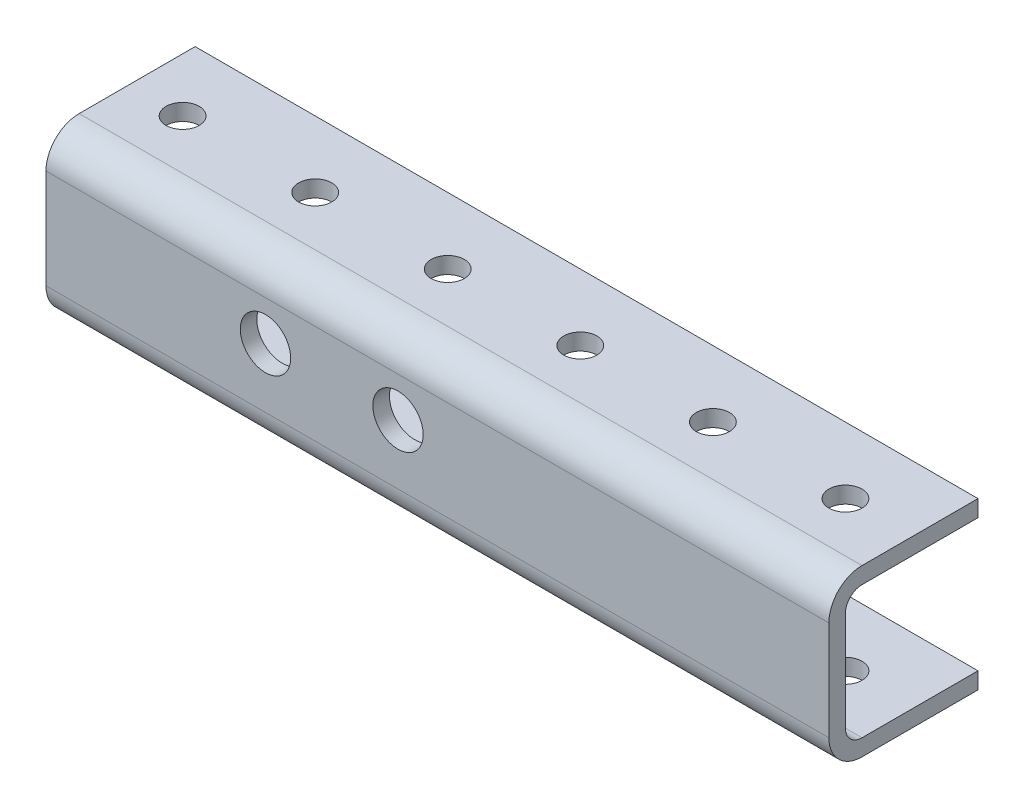
SolidWorks part; units mm, degrees
ref_plane "Front Plane" through (0, 0, 0) normal (0, 0, 1) x (1, 0, 0)
ref_plane "Top Plane" through (0, 0, 0) normal (0, 1, 0) x (1, 0, 0)
ref_plane "Right Plane" through (0, 0, 0) normal (1, 0, 0) x (0, 0, -1)
ref_plane "Plane1" through (0, 0, 3.175) normal (0, 0, 1) x (1, 0, 0)
sketch "Sketch1" plane through (0, 0, 3.175) normal (0, 0, 1) x (1, 0, 0)
  line L0 (872.98, -7.202) -> (872.98, 24.548)
  line L1 (872.98, 24.548) -> (-16.02, 24.548)
  line L2 (-16.02, 24.548) -> (-16.02, -7.202)
  line L3 (-16.02, -7.202) -> (872.98, -7.202)
extrude "Extrude1" add sketch "Sketch1" against normal blind 28.575
sketch "Sketch2" plane through (-16.02, 0, 0) normal (-1, 0, 0) x (0, 0, 1)
  line L0 (-25.4, 21.373) -> (-25.4, -4.027)
  line L1 (-25.4, -4.027) -> (0, -4.027)
  line L2 (0, -4.027) -> (0, 21.373)
  line L3 (0, 21.373) -> (-25.4, 21.373)
extrude "Extrude2" cut sketch "Sketch2" against normal up to next
hole_wizard "Hole1" positions "Sketch4" profile "Sketch3" legacy
sketch "Sketch4" plane through (0, 24.548, 0) normal (0, 1, 0) x (-1, 0, 0)
  point P0 (3.32, -12.7)
sketch "Sketch3" plane through (-3.32, 24.548, -12.7) normal (1, 0, 0) x (0, 0, 1)
  line L0 (0, 0) -> (0, 3.175)
  line L1 (0, 3.175) -> (3.175, 3.175)
  line L2 (3.175, 3.175) -> (3.175, 0)
  line L3 (3.175, 0) -> (0, 0)
  line L4 (0, 110) -> (0, -10) construction
  dimension "Diameter" = 6.35
  dimension "Depth" = 3.175
sketch3d "3DSketch1"
  point P0 (428.6664, 8.6668, -7.2024)
  point P1 (528.6664, 8.6668, -7.2024)
ref_axis "Axis1" through (528.6664, 8.6668, -7.2024) along (-1, 0, 0)
pattern_linear "LPattern1" count 35 spacing 25.4 along (1, 0, 0) of "Hole1"
hole_wizard "Hole2" positions "Sketch6" profile "Sketch5" legacy
sketch "Sketch6" plane through (0, 0, 3.175) normal (0, 0, 1) x (1, 0, 0)
  point P0 (66.53, 10.578)
sketch "Sketch5" plane through (66.53, 10.578, 3.175) normal (1, 0, 0) x (0, -1, 0)
  line L0 (0, 0) -> (0, 3.175)
  line L1 (0, 3.175) -> (4.826, 3.175)
  line L2 (4.826, 3.175) -> (4.826, 0)
  line L3 (4.826, 0) -> (0, 0)
  line L4 (0, 110) -> (0, -10) construction
  dimension "Diameter" = 9.652
  dimension "Depth" = 3.175
sketch3d "3DSketch2"
  point P0 (428.8468, 8.4517, -7.1294)
  point P1 (528.8468, 8.4517, -7.1294)
ref_axis "Axis2" through (528.8468, 8.4517, -7.1294) along (-1, 0, 0)
pattern_linear "LPattern2" count 12 spacing 25.4 along (1, 0, 0) skipping (2, 0), (3, 0), (4, 0), (5, 0), (6, 0), (7, 0), (8, 0), (9, 0) of "Hole2"
hole_wizard "Hole3" positions "Sketch8" profile "Sketch7" legacy
sketch "Sketch8" plane through (0, 0, 3.175) normal (0, 0, 1) x (1, 0, 0)
  point P0 (428.48, 6.768)
sketch "Sketch7" plane through (428.48, 6.768, 3.175) normal (1, 0, 0) x (0, -1, 0)
  line L0 (0, 0) -> (0, 3.175)
  line L1 (0, 3.175) -> (4.826, 3.175)
  line L2 (4.826, 3.175) -> (4.826, 0)
  line L3 (4.826, 0) -> (0, 0)
  line L4 (0, 110) -> (0, -10) construction
  dimension "Diameter" = 9.652
  dimension "Depth" = 3.175
hole_wizard "Hole4" positions "Sketch10" profile "Sketch9" legacy
sketch "Sketch10" plane through (0, 0, 3.175) normal (0, 0, 1) x (1, 0, 0)
  point P0 (511.03, 10.578)
sketch "Sketch9" plane through (511.03, 10.578, 3.175) normal (1, 0, 0) x (0, -1, 0)
  line L0 (0, 0) -> (0, 3.175)
  line L1 (0, 3.175) -> (4.826, 3.175)
  line L2 (4.826, 3.175) -> (4.826, 0)
  line L3 (4.826, 0) -> (0, 0)
  line L4 (0, 110) -> (0, -10) construction
  dimension "Diameter" = 9.652
  dimension "Depth" = 3.175
sketch3d "3DSketch3"
  point P0 (429.3014, 8.4448, -7.1738)
  point P1 (529.3014, 8.4448, -7.1738)
ref_axis "Axis3" through (529.3014, 8.4448, -7.1738) along (-1, 0, 0)
pattern_linear "LPattern3" count 12 spacing 25.4 along (1, 0, 0) skipping (2, 0), (3, 0), (4, 0), (5, 0), (6, 0), (7, 0), (8, 0), (9, 0) of "Hole4"
hole_wizard "Hole5" positions "Sketch12" profile "Sketch11" legacy
sketch "Sketch12" plane through (0, 0, 3.175) normal (0, 0, 1) x (1, 0, 0)
  point P0 (669.78, 8.673)
sketch "Sketch11" plane through (669.78, 8.673, 3.175) normal (1, 0, 0) x (0, -1, 0)
  line L0 (0, 0) -> (0, 3.175)
  line L1 (0, 3.175) -> (1.5875, 3.175)
  line L2 (1.5875, 3.175) -> (1.5875, 0)
  line L3 (1.5875, 0) -> (0, 0)
  line L4 (0, 110) -> (0, -10) construction
  dimension "Diameter" = 3.175
  dimension "Depth" = 3.175
hole_wizard "Hole6" positions "Sketch14" profile "Sketch13" legacy
sketch "Sketch14" plane through (0, -4.027, 0) normal (0, 1, 0) x (-1, 0, 0)
  point P0 (3.32, -12.7)
sketch "Sketch13" plane through (-3.32, -4.027, -12.7) normal (1, 0, 0) x (0, 0, 1)
  line L0 (0, 0) -> (0, 3.175)
  line L1 (0, 3.175) -> (3.175, 3.175)
  line L2 (3.175, 3.175) -> (3.175, 0)
  line L3 (3.175, 0) -> (0, 0)
  line L4 (0, 110) -> (0, -10) construction
  dimension "Diameter" = 6.35
  dimension "Depth" = 3.175
sketch3d "3DSketch4"
  point P0 (428.6444, 8.4444, -7.1991)
  point P1 (528.6444, 8.4444, -7.1991)
ref_axis "Axis4" through (528.6444, 8.4444, -7.1991) along (-1, 0, 0)
pattern_linear "LPattern4" count 35 spacing 25.4 along (1, 0, 0) of "Hole6"
fillet "Fillet1" radius 3.175 1 edges at (428.48, 21.373, 0) tangent propagation no
fillet "Fillet2" radius 3.175 1 edges at (428.48, -4.027, 0) tangent propagation no
fillet "Fillet3" radius 6.35 1 edges at (428.48, -7.202, 3.175) tangent propagation no
fillet "Fillet4" radius 6.35 1 edges at (428.48, 24.548, 3.175) tangent propagation no
sketch "Sketch15" plane through (0, 24.548, 0) normal (0, 1, 0) x (1, 0, 0)
  line L0 (872.98, 25.4) -> (872.98, 3.175) construction
  line L2 (722.98, 25.4) -> (-76.5909, 25.4)
  line L3 (722.98, 25.4) -> (722.98, -29.1024)
  line L4 (722.98, 97.9552) -> (722.98, -47.1552)
  line L5 (722.98, -29.1024) -> (-76.5909, -29.1024)
  line L6 (-76.5909, 25.4) -> (-76.5909, -29.1024)
  line L8 (722.98, -47.1552) -> (-135.8622, -47.1552)
  line L9 (722.98, -47.1552) -> (722.98, 249.2865)
  line L10 (722.98, 249.2865) -> (-135.8622, 249.2865)
  line L11 (-135.8622, -47.1552) -> (-135.8622, 249.2865)
  point P0 (872.98, 25.4)
  circle M2 centre (-3.32, 12.7) radius 3.175
  line M3 (-16.02, 25.4) -> (-16.02, 3.175)
  line M4 (-16.02, 3.175) -> (872.98, 3.175)
  line M6 (872.98, 25.4) -> (-16.02, 25.4)
  circle M7 centre (47.48, 12.7) radius 3.175
  circle M9 centre (98.28, 12.7) radius 3.175
  circle M11 centre (149.08, 12.7) radius 3.175
  circle M13 centre (199.88, 12.7) radius 3.175
  circle M15 centre (250.68, 12.7) radius 3.175
  circle M17 centre (301.48, 12.7) radius 3.175
  circle M18 centre (326.88, 12.7) radius 3.175
  circle M19 centre (352.28, 12.7) radius 3.175
  circle M20 centre (377.68, 12.7) radius 3.175
  circle M21 centre (403.08, 12.7) radius 3.175
  circle M22 centre (428.48, 12.7) radius 3.175
  circle M23 centre (453.88, 12.7) radius 3.175
  circle M24 centre (479.28, 12.7) radius 3.175
  circle M25 centre (504.68, 12.7) radius 3.175
  circle M26 centre (530.08, 12.7) radius 3.175
  circle M27 centre (555.48, 12.7) radius 3.175
  circle M28 centre (580.88, 12.7) radius 3.175
  circle M29 centre (606.28, 12.7) radius 3.175
  circle M30 centre (631.68, 12.7) radius 3.175
  circle M31 centre (657.08, 12.7) radius 3.175
  circle M32 centre (682.48, 12.7) radius 3.175
  circle M33 centre (707.88, 12.7) radius 3.175
  dimension "D1" = 150
extrude "Cut-Extrude4" cut sketch "Sketch15" against normal blind 92 and the other way blind 77 contours L2 L6 L5 L3 M4 M3 | L3 M6 M3 M4 M2 M7 M9 M11 M13 M15 M17 M19 M21 M23 M25 M27 M29 M31 M33 M32 M30 M28 M26 M24 M22 M20 M18 region at (715.5867, 24.548, -14.2875) region at (304.8764, 24.548, 11.6127)
